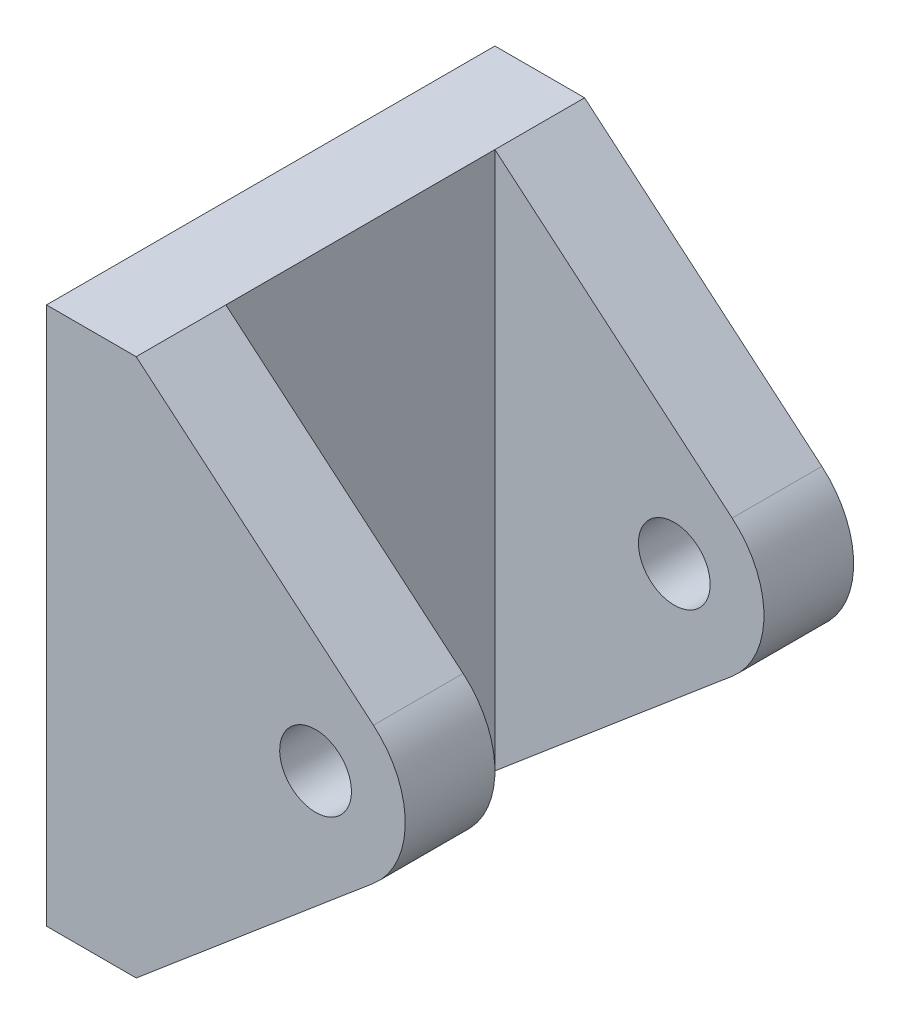
SolidWorks part; units mm, degrees
ref_plane "Ön Düzlem" through (0, 0, 0) normal (0, 0, 1) x (1, 0, 0)
ref_plane "Üst Düzlem" through (0, 0, 0) normal (0, 1, 0) x (1, 0, 0)
ref_plane "Sağ Düzlem" through (0, 0, 0) normal (1, 0, 0) x (0, 0, -1)
sketch "Sketch1" plane through (0, 0, 0) normal (0, 0, 1) x (1, 0, 0)
  line L0 (0, 0) -> (-30, 0)
  line L1 (-30, 30) -> (-20, 30)
  line L2 (-30, 30) -> (-30, -30)
  line L3 (-20, 30) -> (6.4556, 7.6371)
  line L4 (-30, -30) -> (-20, -30)
  line L5 (-20, -30) -> (6.4556, -7.6371)
  circle A0 centre (0, 0) radius 4
  circle A1 centre (0, 0) radius 10
  dimension "D1" = 8
  dimension "D4" = 20
  dimension "D2" = 30
  dimension "D3" = 10
  dimension "D5" = 30
extrude "Boss-Extrude1" add sketch "Sketch1" along normal blind 50 contours A1 L3 L1 L2 L0 | A1 L0 L2 L4 L5 | A1 A0 region at (-4.0907, 8.8142, 0) region at (-18.235, -13.8338, 0) region at (-18.235, 13.8338, 0)
sketch "Sketch2" plane through (0, 0, 0) normal (1, 0, 0) x (0, 0, -1)
  line L0 (-50, 30) -> (-50, 7.6371) construction
  line L1 (-40, 30) -> (-10, 30)
  line L2 (-40, 30) -> (-40, -30)
  line L3 (-40, -30) -> (-10, -30)
  line L4 (-10, 30) -> (-10, -30)
  line L5 (-40, 30) -> (-10, -30) construction
  line L6 (-40, -30) -> (-10, 30) construction
  line L7 (0, 30) -> (0, 7.6371) construction
  line L10 (-50, 30) -> (0, 30) construction
  line L11 (-50, -30) -> (0, -30) construction
  point P0 (-25, 0)
  dimension "D1" = 10
  dimension "D2" = 10
extrude "Cut-Extrude1" cut sketch "Sketch2" against normal up to vertex (20 mm away) and the other way blind 40 up to point (-20, 30, 50)
